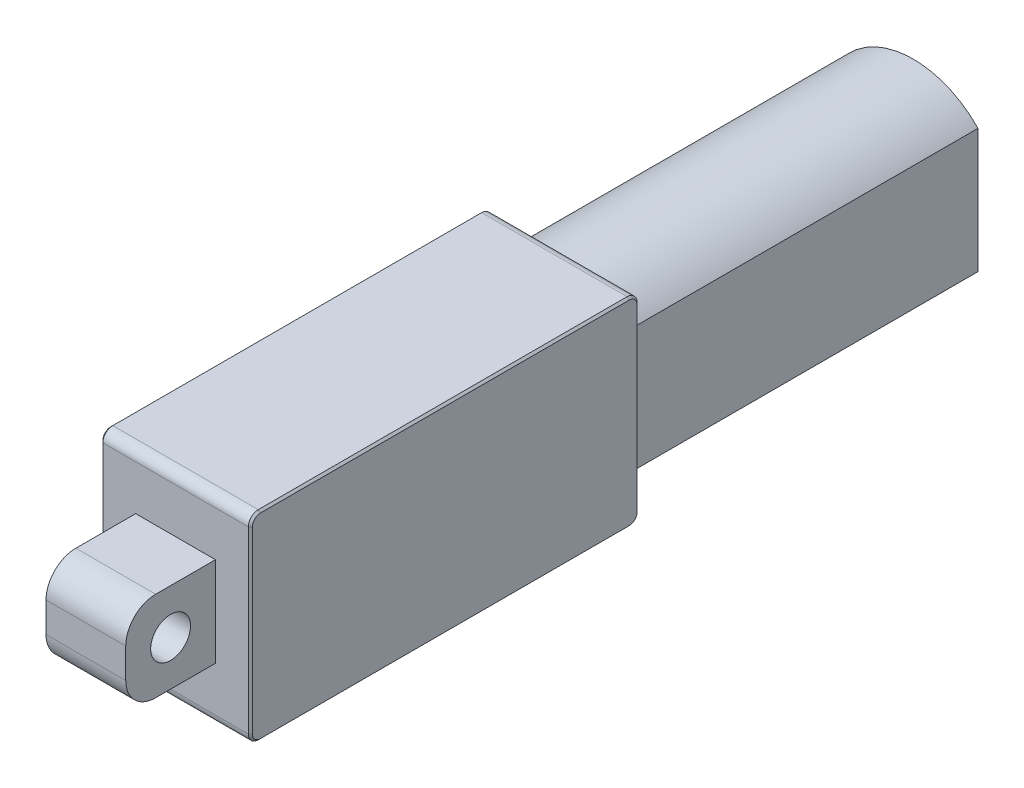
SolidWorks part; units mm, degrees
material "1350 合金"
ref_plane "前视基准面" through (0, 0, 0) normal (0, 0, 1) x (1, 0, 0)
ref_plane "上视基准面" through (0, 0, 0) normal (0, 1, 0) x (1, 0, 0)
ref_plane "右视基准面" through (0, 0, 0) normal (1, 0, 0) x (0, 0, -1)
sketch "草图1" plane through (0, 0, 0) normal (1, 0, 0) x (0, 0, -1)
  line L0 (0, 0) -> (0, 4.5) construction
  line L1 (0, 4.5) -> (4.5, 4.5)
  line L2 (4.5, 4.5) -> (4.5, -4.5)
  line L3 (4.5, -4.5) -> (-1.5, -4.5)
  line L4 (-4.5, -1.5) -> (-4.5, 1.5)
  line L5 (-1.5, 4.5) -> (0, 4.5)
  circle A0 centre (0, 0) radius 2
  arc A1 (-1.5, -4.5) -> (-4.5, -1.5) centre (-1.5, -1.5) cw
  arc A2 (-4.5, 1.5) -> (-1.5, 4.5) centre (-1.5, 1.5) cw
  point P10 (-4.5, -4.5)
  dimension "D1" = 4
  dimension "D6" = 3
  dimension "D2" = 4.5
  dimension "D3" = 4.5
  dimension "D4" = 9
  dimension "D5" = 9
extrude "凸台-拉伸1" add sketch "草图1" along normal blind 8
sketch "草图2" plane through (0, 0, -4.5) normal (0, 0, -1) x (-1, 0, 0)
  line L0 (-4, 4.5) -> (-4, -5.028) construction
  line L1 (-8, 4.5) -> (0, 4.5) construction
  line L2 (-8, 0) -> (3.818, 0) construction
  line L3 (-8, -4.5) -> (-8, 4.5) construction
  line L4 (-4, 4.5) -> (-4, 10) construction
  line L5 (-4, 10) -> (3.5, 10)
  line L6 (3.5, 10) -> (3.5, -10)
  line L7 (3.5, -10) -> (-11.5, -10)
  line L8 (-11.5, -10) -> (-11.5, 10)
  line L9 (-11.5, 10) -> (-4, 10)
  dimension "D1" = 5.5
  dimension "D2" = 7.5
  dimension "D3" = 20
  dimension "D4" = 15
extrude "凸台-拉伸2" add sketch "草图2" along normal blind 39
sketch "草图3" plane through (0, 0, -43.5) normal (0, 0, -1) x (-1, 0, 0)
  line L0 (-11.5, 10) -> (3.5, -10) construction
  line L1 (3.5, 10) -> (-11.5, -10) construction
  line L2 (-4, 10) -> (-4, -10.7224) construction
  line L3 (3.5, 10) -> (-11.5, 10) construction
  line L4 (2.5, 6.2249) -> (2.5, -6.2249)
  line L6 (-10.5, 6.2249) -> (-10.5, -6.2249)
  arc A0 (2.5, 6.2249) -> (-10.5, 6.2249) centre (-4, 0) ccw
  arc A1 (-10.5, -6.2249) -> (2.5, -6.2249) centre (-4, 0) ccw
  point P14 (-10.5, 10)
  point P15 (-10.5, -10.7224)
  point P16 (2.5, 10)
  point P17 (2.5, -10.7224)
  dimension "D1" = 18
  dimension "D2" = 6.5
  dimension "D3" = 6.5
extrude "凸台-拉伸3" add sketch "草图3" along normal blind 35
sketch "草图4" plane through (0, 0, -78.5) normal (0, 0, -1) x (-1, 0, 0)
  circle A0 centre (-4, 0) radius 4.5
  dimension "D1" = 9
extrude "切除-拉伸1" cut sketch "草图4" against normal blind 55
fillet "圆角1" radius 1 4 edges at (4, -10, -4.5) (4, -10, -43.5) (4, 10, -43.5) (4, 10, -4.5)
chamfer "倒角1" distance 0.2 angle 45 16 edges at (-3.5, -10, -24) (-3.5, -9.7071, -43.2071) (-3.5, -9.7071, -4.7929) (-3.5, 0, -43.5) (-3.5, 0, -4.5) (-3.5, 9.7071, -43.2071) (-3.5, 9.7071, -4.7929) (-3.5, 10, -24) (11.5, -10, -24) (11.5, -9.7071, -43.2071) (11.5, -9.7071, -4.7929) (11.5, 0, -43.5) (11.5, 0, -4.5) (11.5, 9.7071, -43.2071) (11.5, 9.7071, -4.7929) (11.5, 10, -24)
